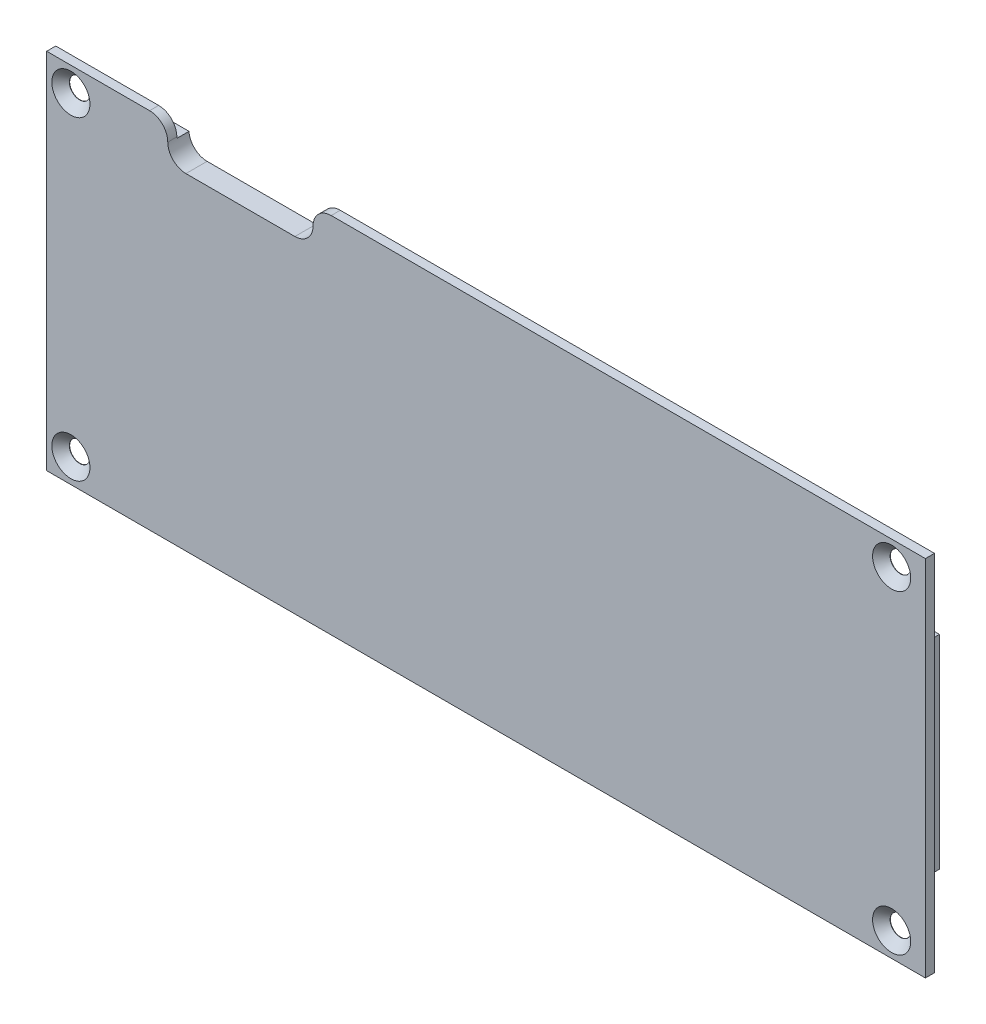
SolidWorks part; units mm, degrees
ref_plane "Plan de face" through (0, 0, 0) normal (0, 0, 1) x (1, 0, 0)
ref_plane "Plan de dessus" through (0, 0, 0) normal (0, 1, 0) x (1, 0, 0)
ref_plane "Plan de droite" through (0, 0, 0) normal (1, 0, 0) x (0, 0, -1)
sketch "Esquisse1" plane through (0, 0, 0) normal (0, 0, 1) x (1, 0, 0)
  line L1 (72.5741, -30) -> (-72.5741, -30)
  line L2 (72.5741, -30) -> (72.5741, 30)
  line L3 (72.5741, 30) -> (-72.5741, 30)
  line L4 (-72.5741, -30) -> (-72.5741, 30)
  line L5 (72.5741, -30) -> (-72.5741, 30) construction
  line L6 (72.5741, 30) -> (-72.5741, -30) construction
  point P0 (0, 0)
  dimension "D1" = 60
  dimension "D2" = 145.1482
extrude "Boss.-Extru.1" add sketch "Esquisse1" along normal blind 1.5
sketch "Esquisse2" plane through (0, 0, 0) normal (0, 0, -1) x (-1, 0, 0)
  line L0 (-71.3741, -16.8) -> (-71.3741, 16.8)
  line L1 (-61.3741, 26.8) -> (61.3741, 26.8)
  line L2 (71.3741, 16.8) -> (71.3741, -16.8)
  line L3 (61.3741, -26.8) -> (-61.3741, -26.8)
  line L4 (-72.5741, 30) -> (72.5741, 30) construction
  line L5 (72.5741, -30) -> (-72.5741, -30) construction
  line L6 (-72.5741, -30) -> (-72.5741, 30) construction
  line L7 (72.5741, 30) -> (72.5741, -30) construction
  arc A0 (-71.3741, 16.8) -> (-61.3741, 26.8) centre (-71.3741, 26.8) ccw
  arc A1 (-71.3741, -16.8) -> (-61.3741, -26.8) centre (-71.3741, -26.8) cw
  arc A2 (71.3741, -16.8) -> (61.3741, -26.8) centre (71.3741, -26.8) ccw
  arc A3 (61.3741, 26.8) -> (71.3741, 16.8) centre (71.3741, 26.8) ccw
  point P8 (-71.3741, 0)
  point P9 (71.3741, 0)
  point P11 (0, -26.8)
  point P12 (0, 26.8)
  point P23 (0, 0)
  point P26 (0, 0)
  point P27 (0, 0)
  dimension "D5" = 10
  dimension "D1" = 3.2
  dimension "D2" = 3.2
  dimension "D3" = 1.2
  dimension "D4" = 1.2
extrude "Boss.-Extru.2" add sketch "Esquisse2" along normal blind 2
sketch "Esquisse4" plane through (0, 0, 1.5) normal (0, 0, 1) x (1, 0, 0)
  line L0 (-68.5741, 26) -> (-68.5741, 30) construction
  line L1 (-68.5741, 26) -> (66.9981, 26)
  line L2 (-68.5741, 26) -> (-68.5741, -26)
  line L3 (-68.5741, -26) -> (66.9981, -26)
  line L4 (66.9981, 26) -> (66.9981, -26)
  line L5 (72.5741, 30) -> (-72.5741, 30) construction
  line L6 (-68.5741, -26) -> (-68.5741, -30) construction
  line L7 (-72.5741, -30) -> (72.5741, -30) construction
  line L8 (-72.5741, 30) -> (-72.5741, -30) construction
  line L9 (72.5741, -30) -> (72.5741, 30) construction
  dimension "D1" = 4
  dimension "D2" = 4
  dimension "D3" = 5.576
hole_wizard "Fraisage pour vis à tête fraisée M31" positions "Esquisse3D1" profile "Esquisse5" countersink size "M3" standard "ISO" end condition up to next
sketch3d "Esquisse3D1"
  point P0 (-68.5741, 26, 1.5)
  point P3 (-68.5741, -26, 1.5)
  point P6 (66.9981, 26, 1.5)
  point P9 (66.9981, -26, 1.5)
sketch "Esquisse5" plane through (-68.5741, 26, 1.5) normal (1, 0, 0) x (0, -1, 0)
  line L0 (0, 0) -> (0, 1.5)
  line L1 (0, 1.5) -> (1.7, 1.5)
  line L2 (1.7, 1.5) -> (1.7, 1.45)
  line L3 (1.7, 1.45) -> (3.15, 0)
  line L5 (3.15, 0) -> (0, 0)
  line L6 (-1.7, 1.45) -> (-3.15, 0) construction
  line L11 (0, -6.35) -> (0, 107.95) construction
  dimension "Diamètre du perçage jusqu'au prochain" = 3.4
  dimension "Profondeur du perçage jusqu'au prochain" = 1.5
  dimension "Diamètre du fraisage entrant" = 6.3
  dimension "Angle du fraisage entrant" = 90
sketch "Esquisse6" plane through (0, 0, 1.5) normal (0, 0, 1) x (1, 0, 0)
  line L0 (72.5741, 30) -> (-72.5741, 30) construction
  line L1 (-52.5741, 30) -> (-28.5741, 30)
  line L2 (-52.5741, 30) -> (-52.5741, 24)
  line L3 (-52.5741, 24) -> (-28.5741, 24)
  line L4 (-28.5741, 30) -> (-28.5741, 24)
  line L5 (-72.5741, 30) -> (-72.5741, -30) construction
  dimension "D1" = 6
  dimension "D2" = 24
  dimension "D3" = 20
extrude "Enlèv. mat.-Extru.1" cut sketch "Esquisse6" against normal through all both
fillet "Congé1" radius 3 4 edges at (-28.5741, 30, 0.75) (-28.5741, 24, -0.25) (-52.5741, 30, 0.75) (-52.5741, 24, -0.25)
